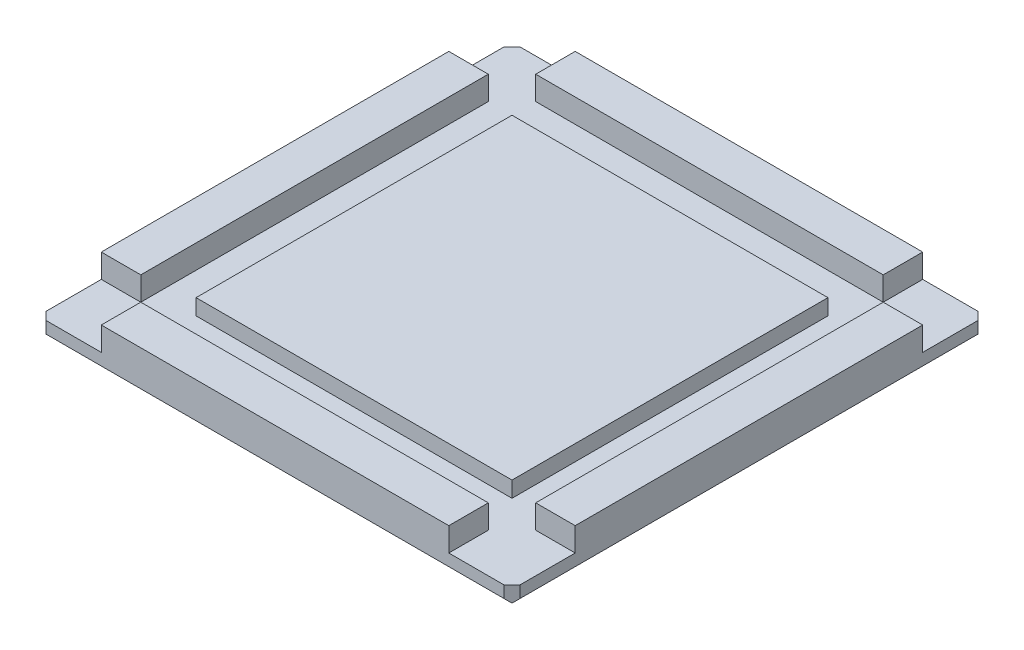
SolidWorks part; units mm, degrees
material "PP 共聚物"
ref_plane "前视基准面" through (0, 0, 0) normal (0, 0, 1) x (1, 0, 0)
ref_plane "上视基准面" through (0, 0, 0) normal (0, 1, 0) x (1, 0, 0)
ref_plane "右视基准面" through (0, 0, 0) normal (1, 0, 0) x (0, 0, -1)
sketch "草图1" plane through (0, 0, 0) normal (0, 1, 0) x (1, 0, 0)
  line L1 (-3, 3) -> (3, 3)
  line L2 (-3, 3) -> (-3, -3)
  line L3 (-3, -3) -> (3, -3)
  line L4 (3, 3) -> (3, -3)
  line L5 (-3, 3) -> (3, -3) construction
  line L6 (-3, -3) -> (3, 3) construction
  point P0 (0, 0)
  dimension "D1" = 6
  dimension "D2" = 6
extrude "凸台-拉伸1" add sketch "草图1" along normal blind 0.2
sketch "草图2" plane through (0, 0.2, 0) normal (0, 1, 0) x (1, 0, 0)
  line L1 (-2, 2) -> (2, 2)
  line L2 (-2, 2) -> (-2, -2)
  line L3 (-2, -2) -> (2, -2)
  line L4 (2, 2) -> (2, -2)
  line L5 (-2, 2) -> (2, -2) construction
  line L6 (-2, -2) -> (2, 2) construction
  point P0 (0, 0)
  dimension "D1" = 4
  dimension "D2" = 4
extrude "凸台-拉伸2" add sketch "草图2" along normal blind 0.2
sketch "草图3" plane through (0, 0.2, 0) normal (0, 1, 0) x (1, 0, 0)
  line L0 (-3, 3) -> (-3, -3) construction
  line L1 (-3, 2.2) -> (-2.5, 2.2)
  line L2 (-3, 2.2) -> (-3, -2.2)
  line L3 (-3, -2.2) -> (-2.5, -2.2)
  line L4 (-2.5, 2.2) -> (-2.5, -2.2)
  line L5 (-3, -3) -> (3, -3) construction
  line L6 (-2.2, -3) -> (2.2, -3)
  line L7 (-2.2, -3) -> (-2.2, -2.5)
  line L8 (-2.2, -2.5) -> (2.2, -2.5)
  line L9 (2.2, -3) -> (2.2, -2.5)
  line L10 (3, -3) -> (3, 3) construction
  line L11 (3, -2.2) -> (2.5, -2.2)
  line L12 (3, -2.2) -> (3, 2.2)
  line L13 (3, 2.2) -> (2.5, 2.2)
  line L14 (2.5, -2.2) -> (2.5, 2.2)
  line L15 (3, 3) -> (-3, 3) construction
  line L16 (2.2, 3) -> (-2.2, 3)
  line L17 (2.2, 3) -> (2.2, 2.5)
  line L18 (2.2, 2.5) -> (-2.2, 2.5)
  line L19 (-2.2, 3) -> (-2.2, 2.5)
  dimension "D1" = 0.5
  dimension "D2" = 0.8
  dimension "D3" = 0.8
  dimension "D4" = 0.8
  dimension "D5" = 0.8
  dimension "D6" = 0.8
  dimension "D7" = 0.8
  dimension "D8" = 0.8
  dimension "D9" = 0.8
  dimension "D10" = 0.5
  dimension "D11" = 0.5
  dimension "D12" = 0.5
extrude "凸台-拉伸3" add sketch "草图3" along normal blind 0.3
chamfer "倒角1" distance 0.05 angle 45 4 edges at (0, 0, -3) (-3, 0, 0) (0, 0, 3) (3, 0, 0)
chamfer "倒角2" distance 0.1 angle 45 4 edges at (3, 0.125, 3) (3, 0.125, -3) (-3, 0.125, -3) (-3, 0.125, 3)
